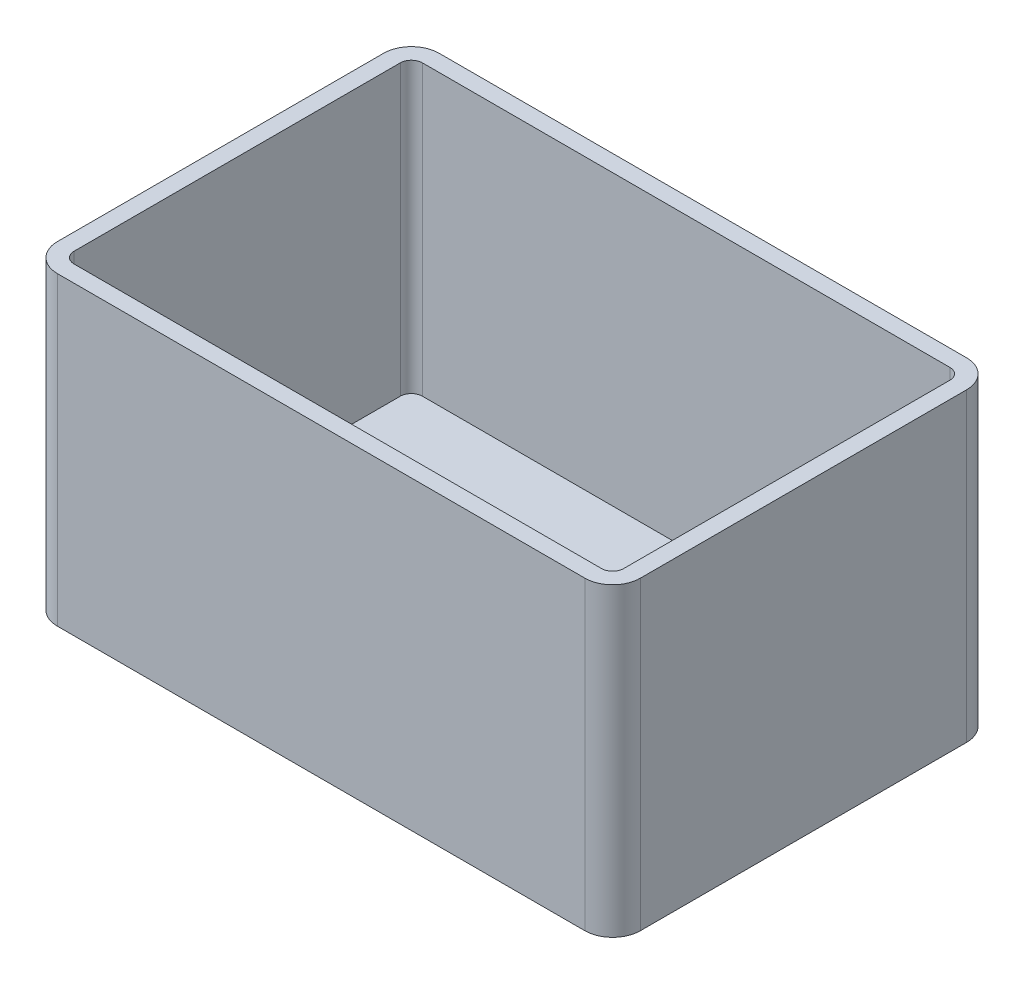
SolidWorks part; units mm, degrees
ref_plane "Front Plane" through (0, 0, 0) normal (0, 0, 1) x (1, 0, 0)
ref_plane "Top Plane" through (0, 0, 0) normal (0, 1, 0) x (1, 0, 0)
ref_plane "Right Plane" through (0, 0, 0) normal (1, 0, 0) x (0, 0, -1)
sketch "Sketch2" plane through (0, 0, 0) normal (0, 1, 0) x (1, 0, 0)
  line L1 (47.5, -34.375) -> (-47.5, -34.375)
  line L2 (52.5, -29.375) -> (52.5, 29.375)
  line L3 (47.5, 34.375) -> (-47.5, 34.375)
  line L4 (-52.5, -29.375) -> (-52.5, 29.375)
  arc A0 (-47.5, -34.375) -> (-52.5, -29.375) centre (-47.5, -29.375) cw
  arc A1 (47.5, -34.375) -> (52.5, -29.375) centre (47.5, -29.375) ccw
  arc A2 (52.5, 29.375) -> (47.5, 34.375) centre (47.5, 29.375) ccw
  arc A3 (-47.5, 34.375) -> (-52.5, 29.375) centre (-47.5, 29.375) ccw
  point P0 (0, 0)
  point P8 (-52.5, -34.375)
  point P13 (52.5, 34.375)
  point P16 (-52.5, 34.375)
  dimension "D3" = 5
  dimension "D1" = 105
  dimension "D2" = 68.75
extrude "Boss-Extrude1" add sketch "Sketch2" along normal blind 55
shell "Shell1" thickness 3 removed face at (0, 55, 0)
sketch "battery_connector_sketch" plane through (0, 3, 0) normal (0, 1, 0) x (1, 0, 0)
  line L0 (-43.2554, -24.8314) -> (-43.2554, -6.8814) construction
  line L1 (-48.2554, -4.8314) -> (-48.2554, -29.1314)
  line L2 (-46.2554, -31.1314) -> (-40.2554, -31.1314)
  line L3 (-40.2554, -2.8314) -> (-46.2554, -2.8314)
  line L4 (-39.5054, -13.4014) -> (-39.5054, -20.5614)
  line L5 (-38.2554, -4.8314) -> (-38.2554, -12.0614)
  line L6 (-38.2554, -29.1314) -> (-38.2554, -21.9014)
  line L7 (-38.2554, -12.0614) -> (-39.5054, -13.4014)
  line L8 (-38.2554, -21.9014) -> (-39.5054, -20.5614)
  line L9 (-41.26, -14.3503) -> (-45.2391, -14.3349)
  arc A0 (-38.2554, -4.8314) -> (-40.2554, -2.8314) centre (-40.2554, -4.8314) ccw
  arc A1 (-48.2554, -29.1314) -> (-46.2554, -31.1314) centre (-46.2554, -29.1314) ccw
  arc A2 (-40.2554, -31.1314) -> (-38.2554, -29.1314) centre (-40.2554, -29.1314) ccw
  arc A3 (-48.2554, -4.8314) -> (-46.2554, -2.8314) centre (-46.2554, -4.8314) cw
  circle A4 centre (-43.2554, -24.8314) radius 2.5
  circle A5 centre (-43.2554, -6.8814) radius 2.5
  arc A6 (-45.2391, -14.3349) -> (-41.26, -14.3503) centre (-43.2554, -15.8564) ccw
  circle A7 centre (-43.2554, -6.8814) radius 2.15
  circle A8 centre (-43.2554, -24.8314) radius 2.15
  dimension "D1" = 4.3
  dimension "D2" = 4.3
extrude "Cut-Extrude1" cut sketch "battery_connector_sketch" against normal blind 2 contours L1 A1 L2 A2 L6 L8 L4 L7 L5 A0 L3 A3
extrude "Cut-Extrude2" cut sketch "battery_connector_sketch<3>" against normal blind 3 contours A7
sketch "battery_connector_sketch<3>" plane through (0, 3, 0) normal (0, 1, 0) x (1, 0, 0) same geometry as "battery_connector_sketch"
extrude "Cut-Extrude3" cut sketch "battery_connector_sketch<4>" against normal blind 3 contours A8
sketch "battery_connector_sketch<4>" plane through (0, 3, 0) normal (0, 1, 0) x (1, 0, 0) same geometry as "battery_connector_sketch"
sketch "Sketch25" plane through (0, 3, 0) normal (0, 1, 0) x (1, 0, 0)
  line L0 (-46.2554, -31.1314) -> (-48.4565, -31.1314)
  line L2 (-46.2554, -2.8314) -> (-49.5, -2.8314)
  line L3 (-49.5, 29.375) -> (-49.5, -29.375) construction
  line L4 (-49.5, -2.8314) -> (-49.5, -29.375)
  line L5 (-48.2554, -29.1314) -> (-48.2554, -4.8314)
  arc A0 (-48.2554, -29.1314) -> (-46.2554, -31.1314) centre (-46.2554, -29.1314) ccw
  arc A1 (-49.5, -29.375) -> (-48.4565, -31.1314) centre (-47.5, -29.375) ccw
  arc A2 (-49.5, -29.375) -> (-47.5, -31.375) centre (-47.5, -29.375) ccw construction
  arc A3 (-48.2554, -4.8314) -> (-46.2554, -2.8314) centre (-46.2554, -4.8314) cw
extrude "Boss-Extrude6" add sketch "Sketch25" along normal blind 12.75
sketch "connector_side_mount_sketch" plane through (-48.2554, 0, 0) normal (1, 0, 0) x (0, 0, -1)
  line L0 (-14.1207, 11.25) -> (-8.6541, 11.25) construction
  line L1 (-4.8314, 1) -> (-29.1314, 1) construction
  line L2 (-2.8314, 15.75) -> (-2.8314, 3) construction
  line L3 (-4.8314, 1) -> (-4.8314, 15.75) construction
  line L5 (-4.8314, 7.2) -> (-29.1314, 7.2)
  line L6 (-4.8314, 7.2) -> (-4.8314, 6)
  line L7 (-4.8314, 6) -> (-29.1314, 6)
  line L8 (-29.1314, 7.2) -> (-29.1314, 6)
  line L9 (-29.1314, 1) -> (-29.1314, 15.75) construction
  circle A0 centre (-9.8914, 11.25) radius 1.55
  circle A1 centre (-24.0714, 11.25) radius 1.505
  line M5 (-4.8314, 1) -> (-4.8314, 15.75)
  line M7 (-29.1314, 15.75) -> (-29.1314, 1)
  dimension "D1" = 3.1
  dimension "D2" = 10.25
  dimension "D4" = 5
  dimension "D3" = 7.06
  dimension "D5" = 1.2
extrude "connector_mount_pins_sockets" cut sketch "connector_side_mount_sketch" against normal blind 2.4 contours A0 | A1
extrude "Boss-Extrude7" add sketch "connector_mount_pins_sockets_sketch<3>" along normal blind 0.7 contours L7 L5 M5 M7 region at (-48.2554, 6.6, 16.9814)
sketch "connector_mount_pins_sockets_sketch<3>" plane through (-48.2554, 0, 0) normal (1, 0, 0) x (0, 0, -1) same geometry as "connector_side_mount_sketch"
